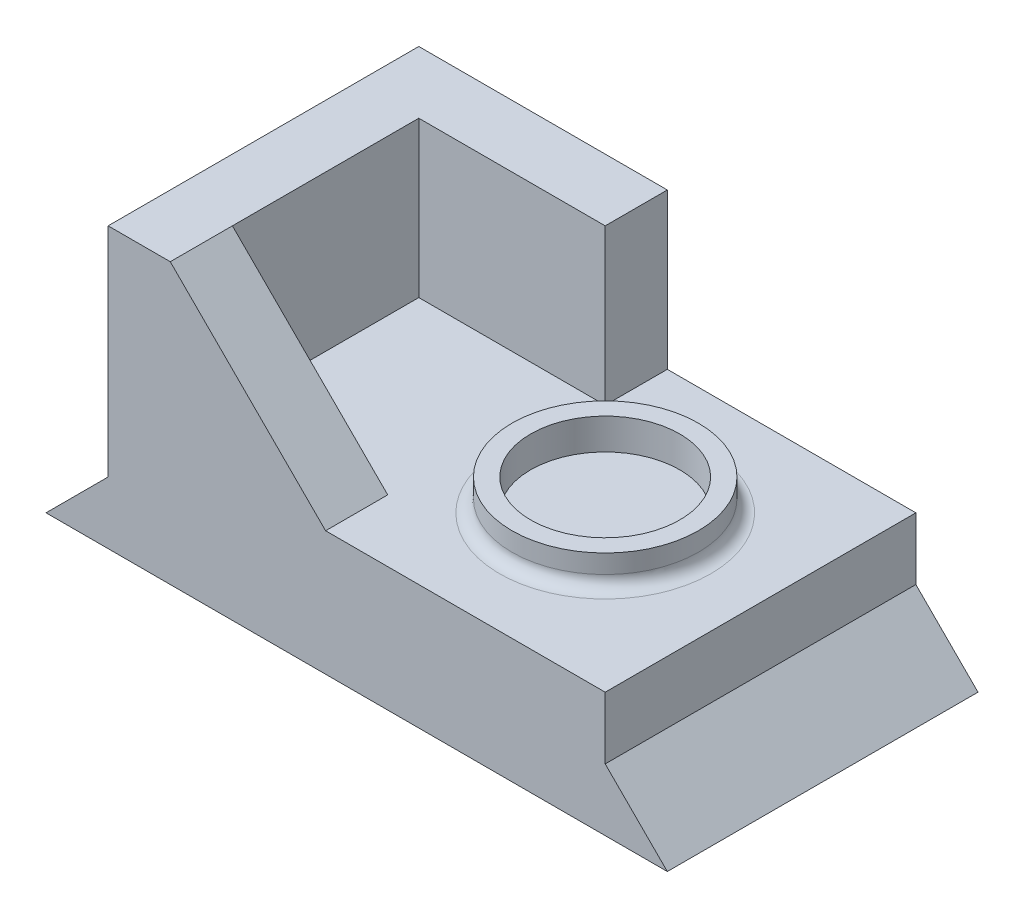
SolidWorks part; units mm, degrees
ref_plane "Front Plane" through (0, 0, 0) normal (0, 0, 1) x (1, 0, 0)
ref_plane "Top Plane" through (0, 0, 0) normal (0, 1, 0) x (1, 0, 0)
ref_plane "Right Plane" through (0, 0, 0) normal (1, 0, 0) x (0, 0, -1)
sketch "Sketch1" plane through (0, 0, 0) normal (0, 0, 1) x (1, 0, 0)
  line L0 (0, 0) -> (100, 0)
  line L1 (100, 0) -> (90, 10)
  line L2 (90, 10) -> (90, 20)
  line L3 (90, 20) -> (10, 20)
  line L4 (45, 20) -> (20, 45)
  line L5 (20, 45) -> (10, 45)
  line L6 (10, 45) -> (10, 10)
  line L7 (10, 10) -> (0, 0)
  point P10 (0, 0)
  point P11 (5.7115, 3.0959)
  dimension "D1" = 100
  dimension "D2" = 10
  dimension "D3" = 10
  dimension "D4" = 10
  dimension "D5" = 10
  dimension "D6" = 45
  dimension "D7" = 10
  dimension "D8" = 25
extrude "Boss-Extrude1" add sketch "Sketch1" along normal blind 50 contours L6 L7 L0 L1 L2 L3 region at (50, 9.6078, 0)
extrude "Boss-Extrude2" add sketch "Sketch1<4>" against normal blind 10 from surface contours L5 L6 L3 L4 region at (22.4074, 30.1852, 0) starting at face at (50, 10, 50)
sketch "Sketch1<4>" plane through (0, 0, 0) normal (0, 0, 1) x (1, 0, 0) same geometry as "Sketch1"
sketch "Sketch2" plane through (0, 20, 0) normal (0, 1, 0) x (1, 0, 0)
  line L0 (20, -40) -> (20, -10)
  line L1 (20, -10) -> (50, -10)
  line L2 (50, -10) -> (50, 0)
  line L4 (90, -50) -> (45, -50) construction
  line L5 (100, -50) -> (100, 0) construction
  line L6 (10, 0) -> (10, -40)
  line L7 (10, -40) -> (45, -40)
  line L8 (45, -40) -> (45, -50)
  line L9 (45, -50) -> (90, -50)
  line L10 (90, -50) -> (90, 0)
  line L11 (90, 0) -> (10, 0)
  line L12 (10, 0) -> (10, -40)
  line L13 (10, -40) -> (20, -40)
  line L17 (50, 0) -> (10, 0)
  circle A0 centre (65, -25) radius 12
  circle A1 centre (65, -25) radius 15
  point P6 (50, -5)
  line M12 (10, 0) -> (10, -40)
  line M13 (10, -40) -> (45, -40)
  line M17 (90, 0) -> (10, 0)
  dimension "D4" = 30
  dimension "D5" = 24
  dimension "D2" = 10
  dimension "D3" = 30
  dimension "D6" = 25
  dimension "D7" = 35
  dimension "D1" = 0
extrude "Boss-Extrude3" add sketch "Sketch2" along normal blind 5 contours A1 A0 region at (50.4243, 20, 25)
extrude "Boss-Extrude4" add sketch "Sketch2<3>" along normal up to surface (25 mm away) contours L1 L2 L0 M17 M12 M13 region at (15, 20, 39.4343) up to face at (15, 45, 45)
sketch "Sketch2<3>" plane through (0, 20, 0) normal (0, 1, 0) x (1, 0, 0) same geometry as "Sketch2"
fillet "Fillet1" radius 2 1 edges at (80, 20, 25)
